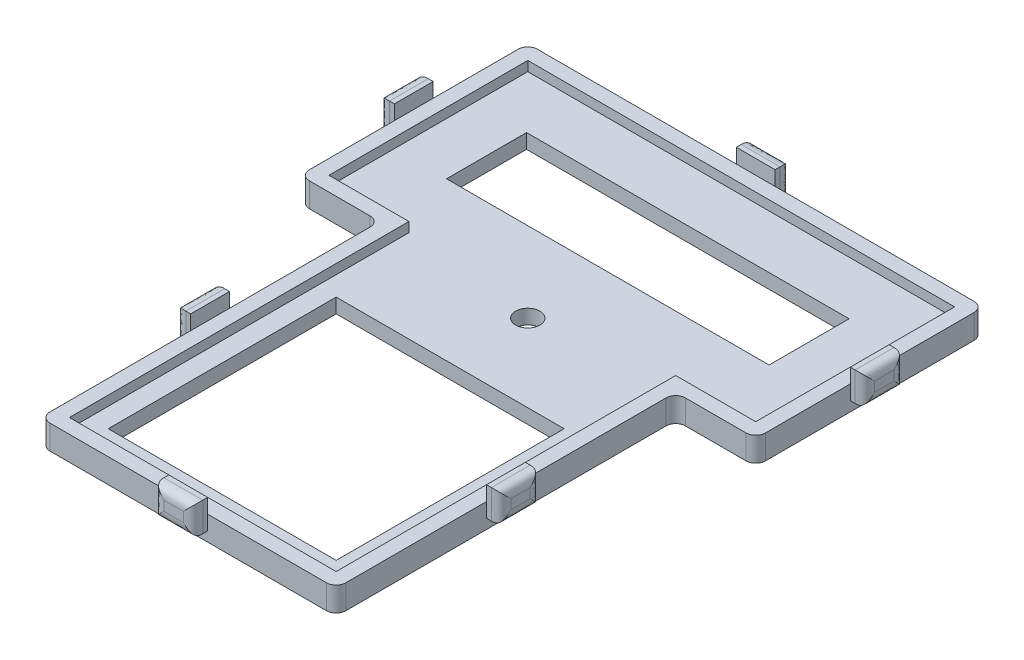
SolidWorks part; units mm, degrees
ref_plane "Front Plane" through (0, 0, 0) normal (0, 0, 1) x (1, 0, 0)
ref_plane "Top Plane" through (0, 0, 0) normal (0, 1, 0) x (1, 0, 0)
ref_plane "Right Plane" through (0, 0, 0) normal (1, 0, 0) x (0, 0, -1)
sketch "Sketch1" plane through (0, 0, 0) normal (0, 1, 0) x (1, 0, 0)
  line L0 (0, 0) -> (88, 0)
  line L1 (88, 0) -> (88, -41)
  line L2 (88, -41) -> (71.5, -41)
  line L3 (71.5, -41) -> (71.5, -111)
  line L4 (71.5, -111) -> (16.5, -111)
  line L5 (16.5, -111) -> (16.5, -41)
  line L6 (16.5, -41) -> (0, -41)
  line L7 (0, -41) -> (0, 0)
  dimension "D1" = 88
  dimension "D2" = 41
  dimension "D3" = 70
  dimension "D4" = 0
  dimension "D5" = 55
extrude "Boss-Extrude2" add sketch "Sketch1" along normal blind 2
shell "Shell1" thickness 3 removed face at (44, 2, 48.25) outward yes
sketch "Sketch2" plane through (0, 0, 0) normal (0, 1, 0) x (1, 0, 0)
  line L1 (44, 0) -> (44, -111) construction
  line L2 (88, 0) -> (0, 0) construction
  line L3 (16.5, -111) -> (71.5, -111) construction
  line L4 (88, 0) -> (0, 0) construction
  line L5 (10.75, -11) -> (77.25, -11)
  line L6 (10.75, -11) -> (10.75, -27.5)
  line L7 (10.75, -27.5) -> (77.25, -27.5)
  line L8 (77.25, -11) -> (77.25, -27.5)
  line L9 (10.75, -11) -> (77.25, -27.5) construction
  line L10 (10.75, -27.5) -> (77.25, -11) construction
  point P0 (44, -19.25)
  dimension "D1" = 11
  dimension "D2" = 16.5
  dimension "D3" = 66.5
extrude "Cut-Extrude1" cut sketch "Sketch2" against normal blind 5
sketch "Sketch3" plane through (0, 0, 0) normal (0, 1, 0) x (1, 0, 0)
  line L0 (44, 0) -> (44, -111) construction
  line L1 (88, 0) -> (0, 0) construction
  line L2 (16.5, -111) -> (71.5, -111) construction
  line L3 (16.5, -111) -> (71.5, -111) construction
  line L4 (20.5, -60) -> (67.5, -60)
  line L5 (20.5, -60) -> (20.5, -107)
  line L6 (20.5, -107) -> (67.5, -107)
  line L7 (67.5, -60) -> (67.5, -107)
  line L8 (20.5, -60) -> (67.5, -107) construction
  line L9 (20.5, -107) -> (67.5, -60) construction
  point P6 (44, -83.5)
  dimension "D1" = 47
  dimension "D2" = 47
  dimension "D3" = 4
extrude "Cut-Extrude2" cut sketch "Sketch3" against normal blind 5
sketch "Sketch4" plane through (91, 0, 0) normal (1, 0, 0) x (0, 0, -1)
  line L0 (-44, 2) -> (3, 2) construction
  line L1 (-24.5, 5) -> (-16.5, 5)
  line L2 (-24.5, 5) -> (-24.5, -1)
  line L3 (-24.5, -1) -> (-16.5, -1)
  line L4 (-16.5, 5) -> (-16.5, -1)
  line L5 (-24.5, 5) -> (-16.5, -1) construction
  line L6 (-24.5, -1) -> (-16.5, 5) construction
  point P0 (-20.5, 2)
  dimension "D1" = 8
  dimension "D2" = 6
extrude "Boss-Extrude3" add sketch "Sketch4" along normal blind 3
ref_plane "Plane1" through (44, 0, 0) normal (-1, 0, 0) x (0, 0, 1)
sketch "Sketch5" plane through (74.5, 0, 0) normal (1, 0, 0) x (0, 0, -1)
  line L0 (-114, 2) -> (-44, 2) construction
  line L1 (-83, 5) -> (-75, 5)
  line L2 (-83, 5) -> (-83, -1)
  line L3 (-83, -1) -> (-75, -1)
  line L4 (-75, 5) -> (-75, -1)
  line L5 (-83, 5) -> (-75, -1) construction
  line L6 (-83, -1) -> (-75, 5) construction
  point P0 (-79, 2)
  dimension "D1" = 8
  dimension "D2" = 6
extrude "Boss-Extrude4" add sketch "Sketch5" along normal blind 3
mirror "Mirror1" about plane through (44, 0, 0) normal (-1, 0, 0) of "Boss-Extrude3", "Boss-Extrude4"
sketch "Sketch6" plane through (0, 0, -3) normal (0, 0, -1) x (-1, 0, 0)
  line L0 (-91, 2) -> (3, 2) construction
  line L1 (-48, 5) -> (-40, 5)
  line L2 (-48, 5) -> (-48, -1)
  line L3 (-48, -1) -> (-40, -1)
  line L4 (-40, 5) -> (-40, -1)
  line L5 (-48, 5) -> (-40, -1) construction
  line L6 (-48, -1) -> (-40, 5) construction
  point P0 (-44, 2)
  dimension "D1" = 8
  dimension "D2" = 6
extrude "Boss-Extrude5" add sketch "Sketch6" along normal blind 3
sketch "Sketch7" plane through (0, 0, 114) normal (0, 0, 1) x (1, 0, 0)
  line L0 (13.5, 2) -> (74.5, 2) construction
  line L10 (40, 5) -> (48, 5)
  line L11 (40, 5) -> (40, -1)
  line L12 (40, -1) -> (48, -1)
  line L13 (48, 5) -> (48, -1)
  line L14 (40, 5) -> (48, -1) construction
  line L15 (40, -1) -> (48, 5) construction
  point P0 (44, -0.2385)
  point P1 (44, -0.2385)
  point P2 (44, 2)
  point P6 (44, 2)
  point P10 (44, 2)
  dimension "D1" = 3
  dimension "D2" = 8
  dimension "D3" = 0
extrude "Boss-Extrude6" add sketch "Sketch7" along normal blind 3
fillet "Fillet4" radius 2 24 edges at (77.5, -1, 79) (77.5, 2, 83) (77.5, 5, 79) (77.5, 2, 75) (44, -1, -6) (48, 2, -6) (44, 5, -6) (40, 2, -6) (-6, 5, 20.5) (-6, 2, 24.5) (-6, -1, 20.5) (-6, 2, 16.5) (10.5, 5, 79) (10.5, 2, 83) (10.5, -1, 79) (10.5, 2, 75) (94, 2, 24.5) (94, -1, 20.5) (94, 2, 16.5) (94, 5, 20.5) (44, -1, 117) (40, 2, 117) (44, 5, 117) (48, 2, 117) curvature continuous yes
fillet "Fillet6" radius 2 8 edges at (74.5, -0.5, 44) (91, -0.5, 44) (91, -0.5, -3) (-3, -0.5, -3) (-3, -0.5, 44) (13.5, -0.5, 44) (13.5, -0.5, 114) (74.5, -0.5, 114)
sketch "Sketch8" plane through (0, -3, 0) normal (0, -1, 0) x (1, 0, 0)
  line L0 (44, 114) -> (44, -3) construction
  line L1 (15.5, 114) -> (72.5, 114) construction
  line L2 (48, -3) -> (40, -3) construction
  line L3 (-1, 44) -> (11.5, 44) construction
  line L4 (5.25, 44) -> (82.75, 44) construction
  circle A0 centre (44, 44) radius 2.5
  point P12 (44, 44)
  dimension "D1" = 5
extrude "Cut-Extrude3" cut sketch "Sketch8" against normal blind 3 contours A0
